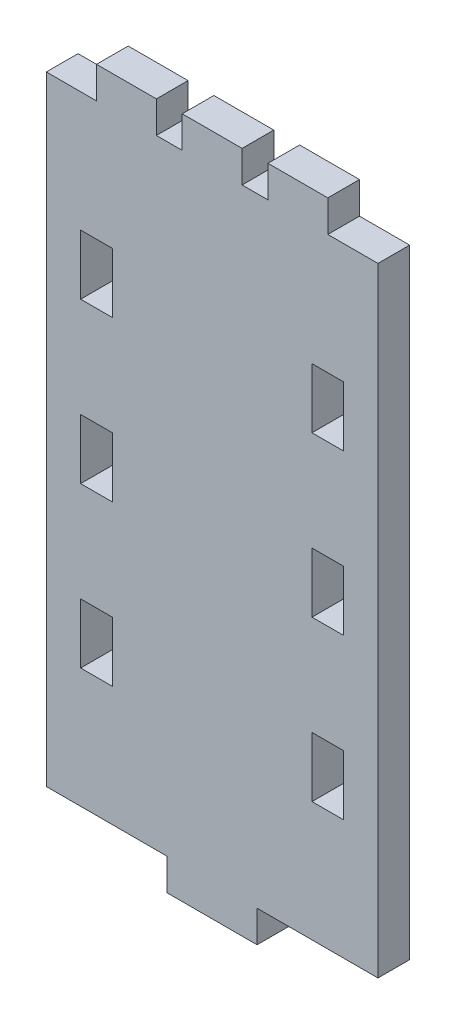
SolidWorks part; units mm, degrees
ref_plane "Front Plane" through (0, 0, 0) normal (0, 0, 1) x (1, 0, 0)
ref_plane "Top Plane" through (0, 0, 0) normal (0, 1, 0) x (1, 0, 0)
ref_plane "Right Plane" through (0, 0, 0) normal (1, 0, 0) x (0, 0, -1)
sketch "Sketch1" plane through (0, 0, 0) normal (0, 0, 1) x (1, 0, 0)
  line L0 (0, 0) -> (-12.1125, 0)
  line L1 (-12.1125, 0) -> (-12.1125, -3.175)
  line L2 (-12.1125, -3.175) -> (-21.1125, -3.175)
  line L3 (-21.1125, -3.175) -> (-21.1125, 0)
  line L4 (-21.1125, 0) -> (-33.225, 0)
  line L5 (-33.225, 0) -> (-33.225, 62)
  line L6 (-33.225, 62) -> (-28.2, 62)
  line L7 (-28.2, 62) -> (-28.2, 65.175)
  line L8 (-28.2, 65.175) -> (-22.2, 65.175)
  line L9 (-22.2, 65.175) -> (-22.2, 62)
  line L10 (-22.2, 62) -> (-19.6125, 62)
  line L11 (-19.6125, 62) -> (-19.6125, 65.175)
  line L12 (-19.6125, 65.175) -> (-13.6125, 65.175)
  line L13 (-13.6125, 65.175) -> (-13.6125, 62)
  line L14 (-13.6125, 62) -> (-11.025, 62)
  line L15 (-11.025, 62) -> (-11.025, 65.175)
  line L16 (-11.025, 65.175) -> (-5.025, 65.175)
  line L17 (-5.025, 65.175) -> (-5.025, 62)
  line L18 (-5.025, 62) -> (0, 62)
  line L19 (0, 62) -> (0, 0)
  line L20 (-16.6125, 62.4063) -> (-16.6125, -5.9437) construction
  line L21 (-16.6125, 65.175) -> (-16.6125, 53.0189) construction
  line L22 (-3.4375, 18) -> (-3.4375, 12)
  line L23 (-3.4375, 18) -> (-6.6125, 18)
  line L24 (-6.6125, 18) -> (-6.6125, 12)
  line L25 (-6.6125, 12) -> (-3.4375, 12)
  line L26 (0, 31) -> (-5.025, 31) construction
  line L27 (-5.025, 18) -> (-5.025, 28) construction
  line L28 (-5.025, 28) -> (-3.4375, 28)
  line L29 (-3.4375, 28) -> (-3.4375, 34)
  line L30 (-3.4375, 34) -> (-6.6125, 34)
  line L31 (-6.6125, 34) -> (-6.6125, 28)
  line L32 (-6.6125, 28) -> (-5.025, 28)
  line L33 (-5.025, 34) -> (-5.025, 44) construction
  line L34 (-5.025, 44) -> (-3.4375, 44)
  line L35 (-3.4375, 44) -> (-3.4375, 50)
  line L36 (-3.4375, 50) -> (-6.6125, 50)
  line L37 (-6.6125, 50) -> (-6.6125, 44)
  line L38 (-6.6125, 44) -> (-5.025, 44)
  line L39 (-28.2, 34) -> (-28.2, 44) construction
  line L40 (-28.2, 18) -> (-28.2, 28) construction
  line L41 (-26.6125, 44) -> (-28.2, 44)
  line L42 (-26.6125, 50) -> (-26.6125, 44)
  line L43 (-29.7875, 50) -> (-26.6125, 50)
  line L44 (-5.025, 50) -> (-5.025, 62) construction
  line L45 (-29.7875, 44) -> (-29.7875, 50)
  line L46 (-28.2, 44) -> (-29.7875, 44)
  line L47 (-26.6125, 28) -> (-28.2, 28)
  line L48 (-26.6125, 34) -> (-26.6125, 28)
  line L49 (-29.7875, 34) -> (-26.6125, 34)
  line L50 (-29.7875, 28) -> (-29.7875, 34)
  line L51 (-28.2, 28) -> (-29.7875, 28)
  line L52 (-26.6125, 12) -> (-29.7875, 12)
  line L53 (-26.6125, 18) -> (-26.6125, 12)
  line L54 (-29.7875, 18) -> (-26.6125, 18)
  line L55 (-5.025, 12) -> (-5.025, 0) construction
  line L56 (-29.7875, 18) -> (-29.7875, 12)
  line L61 (-5, 31) -> (-25.6701, 31) construction
  dimension "D1" = 3.175
  dimension "D2" = 3.4375
  dimension "D3" = 9
  dimension "D4" = 20
  dimension "D5" = 6
  dimension "D8" = 3.175
  dimension "D9" = 6
  dimension "D10" = 10
  dimension "D13" = 62
extrude "Boss-Extrude1" add sketch "Sketch1" along normal mid plane 3.175
